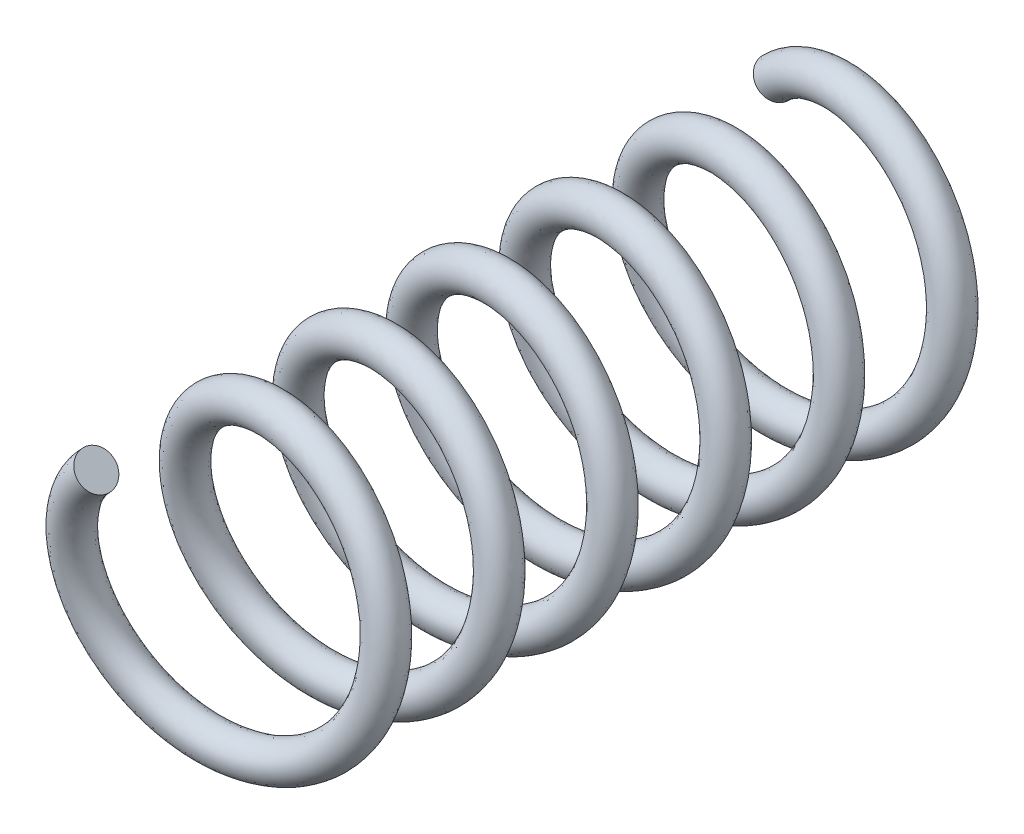
SolidWorks part; units mm, degrees
note: '?' marks a value the reader was unsure of.
material "Acier galvanisé"
ref_plane "Plan de face" through (0, 0, 0) normal (0, 0, 1) x (1, 0, 0)
ref_plane "Plan de dessus" through (0, 0, 0) normal (0, 1, 0) x (1, 0, 0)
ref_plane "Plan de droite" through (0, 0, 0) normal (1, 0, 0) x (0, 0, -1)
sketch "Esquisse1" plane through (0, 0, 0) normal (0, 0, 1) x (1, 0, 0)
  circle A0 centre (0, 0) radius 0.5
  dimension "D1" = 1
curve "Hélice/Spirale1" pitch 4 height 24 turns 6
sketch "Esquisse3" plane through (0, 0, 0) normal (0, 1, 0) x (1, 0, 0)
  circle A0 centre (4.5, 0) radius 0.65
  dimension "D1" = 1.3
  dimension "D2" = 4.5
sweep "Balayage1" add profiles "Esquisse3" path "Hélice/Spirale1"
ref_axis "Axe1" through (0, 0, 0) along (0, 0, 1)?
